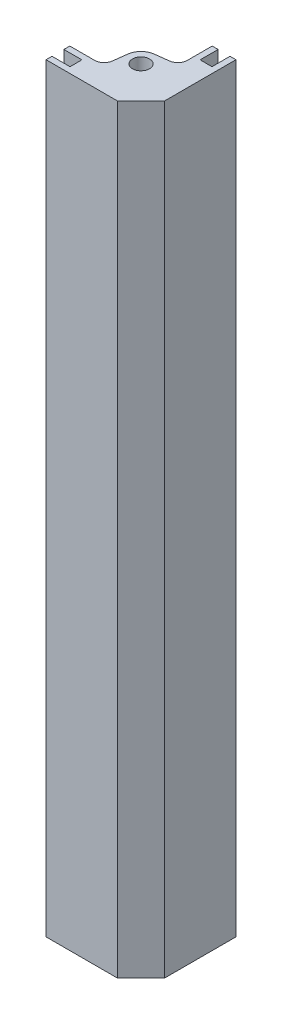
SolidWorks part; units mm, degrees
ref_plane "Front Plane" through (0, 0, 0) normal (0, 0, 1) x (1, 0, 0)
ref_plane "Top Plane" through (0, 0, 0) normal (0, 1, 0) x (1, 0, 0)
ref_plane "Right Plane" through (0, 0, 0) normal (1, 0, 0) x (0, 0, -1)
sketch "Sketch1" plane through (0, 0, 0) normal (0, 1, 0) x (1, 0, 0)
  line L0 (0, 0) -> (25.4, 0)
  line L1 (25.4, 0) -> (25.4, 25.4)
  line L2 (25.4, 25.4) -> (19.05, 25.4)
  line L3 (19.05, 25.4) -> (19.05, 6.35)
  line L4 (19.05, 6.35) -> (0, 6.35)
  line L5 (0, 6.35) -> (0, 0)
  dimension "D1" = 25.4
  dimension "D2" = 6.35
extrude "Boss-Extrude1" add sketch "Sketch1" along normal blind 203.2
sketch "Sketch2" plane through (0, 203.2, 0) normal (0, 1, 0) x (1, 0, 0)
  line L0 (19.05, 25.4) -> (19.05, 6.35) construction
  line L1 (19.05, 6.35) -> (0, 6.35) construction
  line L2 (19.05, 16.51) -> (19.05, 6.35)
  line L3 (19.05, 6.35) -> (8.89, 6.35)
  line L4 (8.89, 6.35) -> (9.6295, 12.244)
  line L5 (19.05, 16.51) -> (13.156, 15.7705)
  line L6 (13.6618, 11.7382) -> (19.05, 6.35) construction
  arc A0 (13.156, 15.7705) -> (9.6295, 12.244) centre (13.6618, 11.7382) ccw
  circle A1 centre (13.6618, 11.7382) radius 2.286
  dimension "D4" = 4.572
  dimension "D5" = 1.778
  dimension "D1" = 45
  dimension "D2" = 10.16
  dimension "D3" = 10.16
  dimension "D6" = 7.62
extrude "Boss-Extrude2" add sketch "Sketch2" against normal blind 6.35
ref_plane "Plane1" through (0, 101.6, 0) normal (0, 1, 0) x (1, 0, 0)
fillet "Fillet1" radius 2.54 2 edges at (19.05, 200.025, -16.51) (8.89, 200.025, -6.35)
mirror "Mirror1" about plane through (0, 101.6, 0) normal (0, 1, 0) of "Fillet1", "Boss-Extrude2"
sketch "Sketch4" plane through (0, 0, 0) normal (0, -1, 0) x (1, 0, 0)
  line L0 (25.4, -25.4) -> (19.05, -25.4) construction
  line L1 (20.6375, -25.4) -> (23.8125, -25.4)
  line L2 (20.6375, -25.4) -> (20.6375, -20.574)
  line L3 (20.6375, -20.574) -> (23.8125, -20.574)
  line L4 (23.8125, -25.4) -> (23.8125, -20.574)
  point P6 (22.225, -25.4)
  point P7 (22.225, -25.4)
  dimension "D1" = 3.175
  dimension "D2" = 4.826
extrude "Cut-Extrude2" cut sketch "Sketch4" against normal through all
sketch "Sketch5" plane through (19.05, 0, 0) normal (-1, 0, 0) x (0, 0, 1)
  line L0 (-25.4, 203.2) -> (-25.4, 0) construction
  line L1 (-25.4, 182.372) -> (-6.35, 182.372) construction
  line L2 (-25.4, 182.372) -> (-25.4, 185.42) construction
  line L3 (-25.4, 185.42) -> (-6.35, 185.42) construction
  line L4 (-6.35, 182.372) -> (-6.35, 185.42) construction
  line L5 (-6.35, 196.85) -> (-6.35, 6.35) construction
  line L6 (-25.4, 179.324) -> (-25.4, 182.372)
  line L7 (-25.4, 176.276) -> (-25.4, 179.324) construction
  line L8 (-25.4, 176.276) -> (-6.35, 176.276) construction
  line L9 (-6.35, 176.276) -> (-6.35, 179.324) construction
  line L10 (-25.4, 179.324) -> (-6.35, 179.324) construction
  line L11 (-25.4, 170.18) -> (-25.4, 173.228) construction
  line L12 (-25.4, 170.18) -> (-6.35, 170.18) construction
  line L13 (-6.35, 170.18) -> (-6.35, 173.228) construction
  line L14 (-25.4, 173.228) -> (-6.35, 173.228) construction
  line L15 (-25.4, 164.084) -> (-25.4, 167.132) construction
  line L16 (-25.4, 164.084) -> (-6.35, 164.084) construction
  line L17 (-6.35, 164.084) -> (-6.35, 167.132) construction
  line L18 (-25.4, 167.132) -> (-6.35, 167.132) construction
  line L19 (-25.4, 157.988) -> (-25.4, 161.036) construction
  line L20 (-25.4, 157.988) -> (-6.35, 157.988) construction
  line L21 (-6.35, 157.988) -> (-6.35, 161.036) construction
  line L22 (-25.4, 161.036) -> (-6.35, 161.036) construction
  line L23 (-25.4, 151.892) -> (-25.4, 154.94) construction
  line L24 (-25.4, 151.892) -> (-6.35, 151.892) construction
  line L25 (-6.35, 151.892) -> (-6.35, 154.94) construction
  line L26 (-25.4, 154.94) -> (-6.35, 154.94) construction
  line L27 (-25.4, 145.796) -> (-25.4, 148.844) construction
  line L28 (-25.4, 145.796) -> (-6.35, 145.796) construction
  line L29 (-6.35, 145.796) -> (-6.35, 148.844) construction
  line L30 (-25.4, 148.844) -> (-6.35, 148.844) construction
  line L31 (-25.4, 139.7) -> (-25.4, 142.748) construction
  line L32 (-25.4, 139.7) -> (-6.35, 139.7) construction
  line L33 (-6.35, 139.7) -> (-6.35, 142.748) construction
  line L34 (-25.4, 142.748) -> (-6.35, 142.748) construction
  line L35 (-25.4, 133.604) -> (-25.4, 136.652) construction
  line L36 (-25.4, 133.604) -> (-6.35, 133.604) construction
  line L37 (-6.35, 133.604) -> (-6.35, 136.652) construction
  line L38 (-25.4, 136.652) -> (-6.35, 136.652) construction
  line L39 (-25.4, 127.508) -> (-25.4, 130.556) construction
  line L40 (-25.4, 127.508) -> (-6.35, 127.508) construction
  line L41 (-6.35, 127.508) -> (-6.35, 130.556) construction
  line L42 (-25.4, 130.556) -> (-6.35, 130.556) construction
  line L43 (-25.4, 121.412) -> (-25.4, 124.46) construction
  line L44 (-25.4, 121.412) -> (-6.35, 121.412) construction
  line L45 (-6.35, 121.412) -> (-6.35, 124.46) construction
  line L46 (-25.4, 124.46) -> (-6.35, 124.46) construction
  line L47 (-25.4, 115.316) -> (-25.4, 118.364) construction
  line L48 (-25.4, 115.316) -> (-6.35, 115.316) construction
  line L49 (-6.35, 115.316) -> (-6.35, 118.364) construction
  line L50 (-25.4, 118.364) -> (-6.35, 118.364) construction
  line L51 (-25.4, 109.22) -> (-25.4, 112.268) construction
  line L52 (-25.4, 109.22) -> (-6.35, 109.22) construction
  line L53 (-6.35, 109.22) -> (-6.35, 112.268) construction
  line L54 (-25.4, 112.268) -> (-6.35, 112.268) construction
  line L55 (-25.4, 103.124) -> (-25.4, 106.172) construction
  line L56 (-25.4, 103.124) -> (-6.35, 103.124) construction
  line L57 (-6.35, 103.124) -> (-6.35, 106.172) construction
  line L58 (-25.4, 106.172) -> (-6.35, 106.172) construction
  line L59 (-25.4, 97.028) -> (-25.4, 100.076) construction
  line L60 (-25.4, 97.028) -> (-6.35, 97.028) construction
  line L61 (-6.35, 97.028) -> (-6.35, 100.076) construction
  line L62 (-25.4, 100.076) -> (-6.35, 100.076) construction
  line L63 (-25.4, 90.932) -> (-25.4, 93.98) construction
  line L64 (-25.4, 90.932) -> (-6.35, 90.932) construction
  line L65 (-6.35, 90.932) -> (-6.35, 93.98) construction
  line L66 (-25.4, 93.98) -> (-6.35, 93.98) construction
  line L67 (-25.4, 84.836) -> (-25.4, 87.884) construction
  line L68 (-25.4, 84.836) -> (-6.35, 84.836) construction
  line L69 (-6.35, 84.836) -> (-6.35, 87.884) construction
  line L70 (-25.4, 87.884) -> (-6.35, 87.884) construction
  line L71 (-25.4, 78.74) -> (-25.4, 81.788) construction
  line L72 (-25.4, 78.74) -> (-6.35, 78.74) construction
  line L73 (-6.35, 78.74) -> (-6.35, 81.788) construction
  line L74 (-25.4, 81.788) -> (-6.35, 81.788) construction
  line L75 (-25.4, 72.644) -> (-25.4, 75.692) construction
  line L76 (-25.4, 72.644) -> (-6.35, 72.644) construction
  line L77 (-6.35, 72.644) -> (-6.35, 75.692) construction
  line L78 (-25.4, 75.692) -> (-6.35, 75.692) construction
  line L79 (-25.4, 66.548) -> (-25.4, 69.596) construction
  line L80 (-25.4, 66.548) -> (-6.35, 66.548) construction
  line L81 (-6.35, 66.548) -> (-6.35, 69.596) construction
  line L82 (-25.4, 69.596) -> (-6.35, 69.596) construction
  line L83 (-25.4, 60.452) -> (-25.4, 63.5) construction
  line L84 (-25.4, 60.452) -> (-6.35, 60.452) construction
  line L85 (-6.35, 60.452) -> (-6.35, 63.5) construction
  line L86 (-25.4, 63.5) -> (-6.35, 63.5) construction
  line L87 (-25.4, 54.356) -> (-25.4, 57.404) construction
  line L88 (-25.4, 54.356) -> (-6.35, 54.356) construction
  line L89 (-6.35, 54.356) -> (-6.35, 57.404) construction
  line L90 (-25.4, 57.404) -> (-6.35, 57.404) construction
  line L91 (-25.4, 48.26) -> (-25.4, 51.308) construction
  line L92 (-25.4, 48.26) -> (-6.35, 48.26) construction
  line L93 (-6.35, 48.26) -> (-6.35, 51.308) construction
  line L94 (-25.4, 51.308) -> (-6.35, 51.308) construction
  line L95 (-25.4, 42.164) -> (-25.4, 45.212) construction
  line L96 (-25.4, 42.164) -> (-6.35, 42.164) construction
  line L97 (-6.35, 42.164) -> (-6.35, 45.212) construction
  line L98 (-25.4, 45.212) -> (-6.35, 45.212) construction
  line L99 (-25.4, 36.068) -> (-25.4, 39.116) construction
  line L100 (-25.4, 36.068) -> (-6.35, 36.068) construction
  line L101 (-6.35, 36.068) -> (-6.35, 39.116) construction
  line L102 (-25.4, 39.116) -> (-6.35, 39.116) construction
  line L103 (-25.4, 29.972) -> (-25.4, 33.02) construction
  line L104 (-25.4, 29.972) -> (-6.35, 29.972) construction
  line L105 (-6.35, 29.972) -> (-6.35, 33.02) construction
  line L106 (-25.4, 33.02) -> (-6.35, 33.02) construction
  line L107 (-25.4, 23.876) -> (-25.4, 26.924) construction
  line L108 (-25.4, 23.876) -> (-6.35, 23.876) construction
  line L109 (-6.35, 23.876) -> (-6.35, 26.924) construction
  line L110 (-25.4, 26.924) -> (-6.35, 26.924) construction
  line L111 (-25.4, 17.78) -> (-25.4, 20.828) construction
  line L112 (-25.4, 17.78) -> (-6.35, 17.78) construction
  line L113 (-6.35, 17.78) -> (-6.35, 20.828) construction
  line L114 (-25.4, 20.828) -> (-6.35, 20.828) construction
  line L115 (-25.4, 185.42) -> (-25.4, 17.78) construction
  line L116 (-25.4, 185.42) -> (-6.35, 185.42)
  line L121 (-25.4, 185.42) -> (-25.4, 188.468)
  line L122 (-25.4, 188.468) -> (-6.35, 188.468)
  line L123 (-6.35, 185.42) -> (-6.35, 188.468)
  line L124 (-25.4, 179.324) -> (-6.35, 179.324)
  line L125 (-6.35, 179.324) -> (-6.35, 182.372)
  line L126 (-25.4, 182.372) -> (-6.35, 182.372)
  line L127 (-25.4, 173.228) -> (-25.4, 176.276)
  line L128 (-25.4, 173.228) -> (-6.35, 173.228)
  line L129 (-6.35, 173.228) -> (-6.35, 176.276)
  line L130 (-25.4, 176.276) -> (-6.35, 176.276)
  line L131 (-25.4, 167.132) -> (-25.4, 170.18)
  line L132 (-25.4, 167.132) -> (-6.35, 167.132)
  line L133 (-6.35, 167.132) -> (-6.35, 170.18)
  line L134 (-25.4, 170.18) -> (-6.35, 170.18)
  line L135 (-25.4, 161.036) -> (-25.4, 164.084)
  line L136 (-25.4, 161.036) -> (-6.35, 161.036)
  line L137 (-6.35, 161.036) -> (-6.35, 164.084)
  line L138 (-25.4, 164.084) -> (-6.35, 164.084)
  line L139 (-25.4, 154.94) -> (-25.4, 157.988)
  line L140 (-25.4, 154.94) -> (-6.35, 154.94)
  line L141 (-6.35, 154.94) -> (-6.35, 157.988)
  line L142 (-25.4, 157.988) -> (-6.35, 157.988)
  line L143 (-25.4, 148.844) -> (-25.4, 151.892)
  line L144 (-25.4, 148.844) -> (-6.35, 148.844)
  line L145 (-6.35, 148.844) -> (-6.35, 151.892)
  line L146 (-25.4, 151.892) -> (-6.35, 151.892)
  line L147 (-25.4, 142.748) -> (-25.4, 145.796)
  line L148 (-25.4, 142.748) -> (-6.35, 142.748)
  line L149 (-6.35, 142.748) -> (-6.35, 145.796)
  line L150 (-25.4, 145.796) -> (-6.35, 145.796)
  line L151 (-25.4, 136.652) -> (-25.4, 139.7)
  line L152 (-25.4, 136.652) -> (-6.35, 136.652)
  line L153 (-6.35, 136.652) -> (-6.35, 139.7)
  line L154 (-25.4, 139.7) -> (-6.35, 139.7)
  line L155 (-25.4, 130.556) -> (-25.4, 133.604)
  line L156 (-25.4, 130.556) -> (-6.35, 130.556)
  line L157 (-6.35, 130.556) -> (-6.35, 133.604)
  line L158 (-25.4, 133.604) -> (-6.35, 133.604)
  line L159 (-25.4, 124.46) -> (-25.4, 127.508)
  line L160 (-25.4, 124.46) -> (-6.35, 124.46)
  line L161 (-6.35, 124.46) -> (-6.35, 127.508)
  line L162 (-25.4, 127.508) -> (-6.35, 127.508)
  line L163 (-25.4, 118.364) -> (-25.4, 121.412)
  line L164 (-25.4, 118.364) -> (-6.35, 118.364)
  line L165 (-6.35, 118.364) -> (-6.35, 121.412)
  line L166 (-25.4, 121.412) -> (-6.35, 121.412)
  line L167 (-25.4, 112.268) -> (-25.4, 115.316)
  line L168 (-25.4, 112.268) -> (-6.35, 112.268)
  line L169 (-6.35, 112.268) -> (-6.35, 115.316)
  line L170 (-25.4, 115.316) -> (-6.35, 115.316)
  line L171 (-25.4, 106.172) -> (-25.4, 109.22)
  line L172 (-25.4, 106.172) -> (-6.35, 106.172)
  line L173 (-6.35, 106.172) -> (-6.35, 109.22)
  line L174 (-25.4, 109.22) -> (-6.35, 109.22)
  line L175 (-25.4, 100.076) -> (-25.4, 103.124)
  line L176 (-25.4, 100.076) -> (-6.35, 100.076)
  line L177 (-6.35, 100.076) -> (-6.35, 103.124)
  line L178 (-25.4, 103.124) -> (-6.35, 103.124)
  line L179 (-25.4, 93.98) -> (-25.4, 97.028)
  line L180 (-25.4, 93.98) -> (-6.35, 93.98)
  line L181 (-6.35, 93.98) -> (-6.35, 97.028)
  line L182 (-25.4, 97.028) -> (-6.35, 97.028)
  line L183 (-25.4, 87.884) -> (-25.4, 90.932)
  line L184 (-25.4, 87.884) -> (-6.35, 87.884)
  line L185 (-6.35, 87.884) -> (-6.35, 90.932)
  line L186 (-25.4, 90.932) -> (-6.35, 90.932)
  line L187 (-25.4, 81.788) -> (-25.4, 84.836)
  line L188 (-25.4, 81.788) -> (-6.35, 81.788)
  line L189 (-6.35, 81.788) -> (-6.35, 84.836)
  line L190 (-25.4, 84.836) -> (-6.35, 84.836)
  line L191 (-25.4, 75.692) -> (-25.4, 78.74)
  line L192 (-25.4, 75.692) -> (-6.35, 75.692)
  line L193 (-6.35, 75.692) -> (-6.35, 78.74)
  line L194 (-25.4, 78.74) -> (-6.35, 78.74)
  line L195 (-25.4, 69.596) -> (-25.4, 72.644)
  line L196 (-25.4, 69.596) -> (-6.35, 69.596)
  line L197 (-6.35, 69.596) -> (-6.35, 72.644)
  line L198 (-25.4, 72.644) -> (-6.35, 72.644)
  line L199 (-25.4, 63.5) -> (-25.4, 66.548)
  line L200 (-25.4, 63.5) -> (-6.35, 63.5)
  line L201 (-6.35, 63.5) -> (-6.35, 66.548)
  line L202 (-25.4, 66.548) -> (-6.35, 66.548)
  line L203 (-25.4, 57.404) -> (-25.4, 60.452)
  line L204 (-25.4, 57.404) -> (-6.35, 57.404)
  line L205 (-6.35, 57.404) -> (-6.35, 60.452)
  line L206 (-25.4, 60.452) -> (-6.35, 60.452)
  line L207 (-25.4, 51.308) -> (-25.4, 54.356)
  line L208 (-25.4, 51.308) -> (-6.35, 51.308)
  line L209 (-6.35, 51.308) -> (-6.35, 54.356)
  line L210 (-25.4, 54.356) -> (-6.35, 54.356)
  line L211 (-25.4, 45.212) -> (-25.4, 48.26)
  line L212 (-25.4, 45.212) -> (-6.35, 45.212)
  line L213 (-6.35, 45.212) -> (-6.35, 48.26)
  line L214 (-25.4, 48.26) -> (-6.35, 48.26)
  line L215 (-25.4, 39.116) -> (-25.4, 42.164)
  line L216 (-25.4, 39.116) -> (-6.35, 39.116)
  line L217 (-6.35, 39.116) -> (-6.35, 42.164)
  line L218 (-25.4, 42.164) -> (-6.35, 42.164)
  line L219 (-25.4, 33.02) -> (-25.4, 36.068)
  line L220 (-25.4, 33.02) -> (-6.35, 33.02)
  line L221 (-6.35, 33.02) -> (-6.35, 36.068)
  line L222 (-25.4, 36.068) -> (-6.35, 36.068)
  line L223 (-25.4, 26.924) -> (-25.4, 29.972)
  line L224 (-25.4, 26.924) -> (-6.35, 26.924)
  line L225 (-6.35, 26.924) -> (-6.35, 29.972)
  line L226 (-25.4, 29.972) -> (-6.35, 29.972)
  line L227 (-25.4, 20.828) -> (-25.4, 23.876)
  line L228 (-25.4, 20.828) -> (-6.35, 20.828)
  line L229 (-6.35, 20.828) -> (-6.35, 23.876)
  line L230 (-25.4, 23.876) -> (-6.35, 23.876)
  line L231 (-25.4, 14.732) -> (-25.4, 17.78)
  line L232 (-25.4, 14.732) -> (-6.35, 14.732)
  line L233 (-6.35, 14.732) -> (-6.35, 17.78)
  line L234 (-25.4, 17.78) -> (-6.35, 17.78)
  point P9 (-6.35, 101.6)
  point P10 (-25.4, 101.6)
  dimension "D1" = 3.048
  dimension "D2" = 3.048
  dimension "D3" = 28
  dimension "D4" = 3.048
  dimension "D5" = 29
extrude "Boss-Extrude3" add sketch "Sketch5" along normal up to surface (19.05 mm away) up to face at (0, 101.6, -3.175)
chamfer "Chamfer1" distance 6.35 angle 45 1 edges at (25.4, 101.6, 0)
sketch "Sketch6" plane through (0, 188.468, 0) normal (0, 1, 0) x (1, 0, 0)
  line L0 (0, 6.35) -> (19.05, 6.35) construction
  line L1 (0, 25.4) -> (14.2875, 25.4)
  line L2 (0, 25.4) -> (0, 11.1125)
  line L3 (0, 11.1125) -> (11.7475, 11.1125)
  line L4 (14.2875, 25.4) -> (14.2875, 13.6525)
  line L5 (11.7475, 11.1125) -> (14.2875, 13.6525)
  line L6 (19.05, 6.35) -> (19.05, 25.4) construction
  point P1 (14.2875, 11.1125)
  dimension "D1" = 4.7625
  dimension "D2" = 4.7625
extrude "Cut-Extrude3" cut sketch "Sketch6" against normal up to surface (173.736 mm away) up to face at (9.525, 14.732, -15.875)
ref_plane "Plane2" through (12.7, 0, -12.7) normal (0.7071, 0, -0.7071) x (-0.7071, 0, -0.7071)
mirror "Mirror2" about plane through (12.7, 0, -12.7) normal (0.7071, 0, -0.7071) of "Cut-Extrude2"
